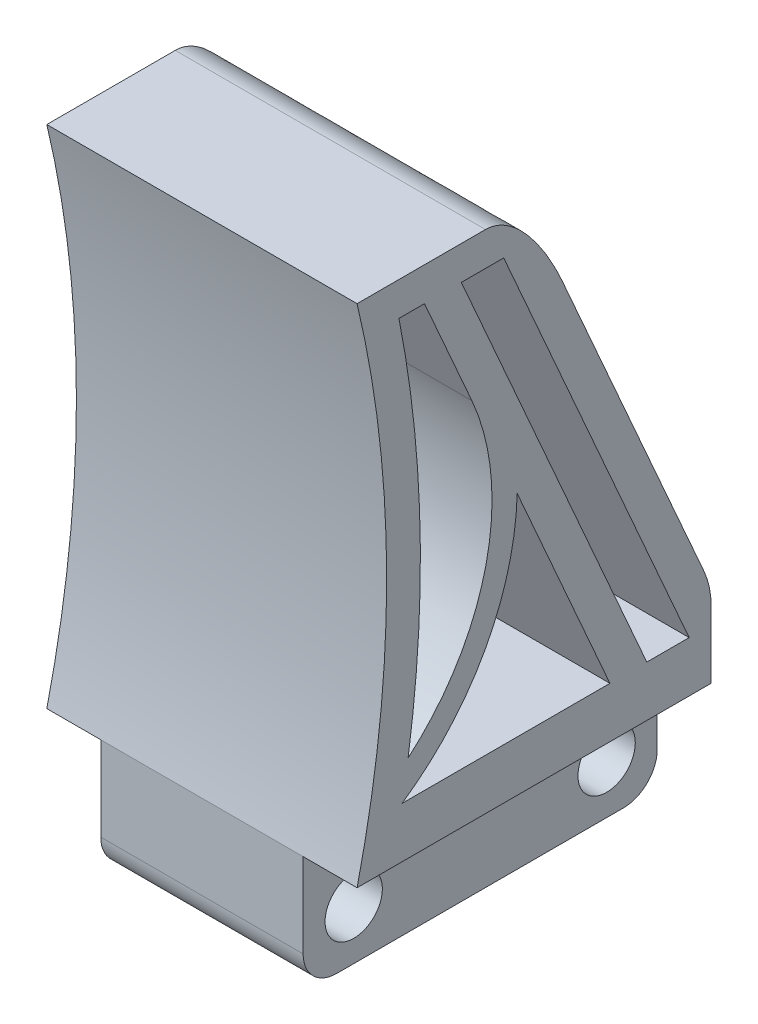
SolidWorks part; units mm, degrees
ref_plane "Front Plane" through (0, 0, 0) normal (0, 0, 1) x (1, 0, 0)
ref_plane "Top Plane" through (0, 0, 0) normal (0, 1, 0) x (1, 0, 0)
ref_plane "Right Plane" through (0, 0, 0) normal (1, 0, 0) x (0, 0, -1)
sketch "Sketch1" plane through (0, 0, 0) normal (1, 0, 0) x (0, 0, -1)
  line L0 (0, 0) -> (21, 0)
  line L4 (10, 30) -> (0, 30)
  line L5 (21, 0) -> (21, 5)
  line L6 (21, 5) -> (10, 30)
  line L7 (8.695, 28) -> (19.695, 3)
  line L9 (17.1822, 3) -> (6.1822, 28)
  line L11 (8.695, 28) -> (6.1822, 28)
  line L12 (17.1822, 3) -> (19.695, 3)
  line L13 (3.9971, 28) -> (14.9971, 3)
  line L14 (14.9971, 3) -> (2.6711, 3)
  line L15 (3.9971, 28) -> (2.4812, 28)
  arc A0 (0, 30) -> (0, 0) centre (-63.2456, 15) cw
  arc A2 (2.4812, 28) -> (2.6711, 3) centre (-63.2456, 15) cw
  arc A3 (6.8055, 21.6173) -> (3.0273, 5.1556) centre (-6.1358, 15.9231) cw
  arc A4 (9.4971, 15.5) -> (2.6711, 3) centre (-6.1358, 15.9231) cw
  point P22 (5.0946, 25.5058)
  point P23 (8.0838, 18.712)
  point P24 (0, 0)
  point P25 (8.695, 17.5843)
  point P26 (9.4971, 15.5)
  dimension "D4" = 5
  dimension "D5" = 65
  dimension "D10" = 2
  dimension "D11" = 2
  dimension "D12" = 1.5
  dimension "D1" = 21
  dimension "D2" = 30
  dimension "D3" = 10
  dimension "D6" = 2.3
  dimension "D7" = 2
  dimension "D8" = 3
  dimension "D9" = 2
extrude "Boss-Extrude1" add sketch "Sketch1" along normal blind 18.4 contours L4 A0 L0 L5 L6 A2 L15 L13 L14 L12 L9 L11 L7 | A4 L13 A3 A2 region at (0, 15, -2.1206) region at (0, 10.3649, -6.9081)
fillet "Fillet1" radius 7 1 edges at (9.2, 30, -10) second distance 5 first distance on face at (9.2, 17.5, -15.5)
fillet "Fillet2" radius 5 1 edges at (9.2, 5, -21)
sketch "Sketch2" plane through (0, 0, 0) normal (0, -1, 0) x (-1, 0, 0)
  line L6 (-18.4, 0) -> (0, 0) construction
  line L7 (-3.2, 0) -> (-15.2, 0)
  line L8 (-3.2, 0) -> (-3.2, 21)
  line L9 (-3.2, 21) -> (-15.2, 21)
  line L10 (-15.2, 0) -> (-15.2, 21)
  line L11 (-18.4, 21) -> (0, 21) construction
  point P8 (-9.2, 21)
  point P9 (-9.2, 21)
  dimension "D1" = 12
extrude "Boss-Extrude2" add sketch "Sketch2" along normal blind 7
sketch "Sketch3" plane through (15.2, 0, 0) normal (1, 0, 0) x (0, 0, -1)
  line L0 (21, -7) -> (0, -7) construction
  line L1 (3, -4) -> (18, -4) construction
  circle A0 centre (3, -4) radius 1.7
  circle A1 centre (18, -4) radius 1.7
  point P4 (10.5, -7)
  point P7 (10.5, -4)
  dimension "D1" = 15
  dimension "D2" = 3
  dimension "D3" = 3.4
extrude "Cut-Extrude1" cut sketch "Sketch3" against normal through all
fillet "Fillet3" radius 2 2 edges at (9.2, -7, 0) (9.2, -7, -21)
